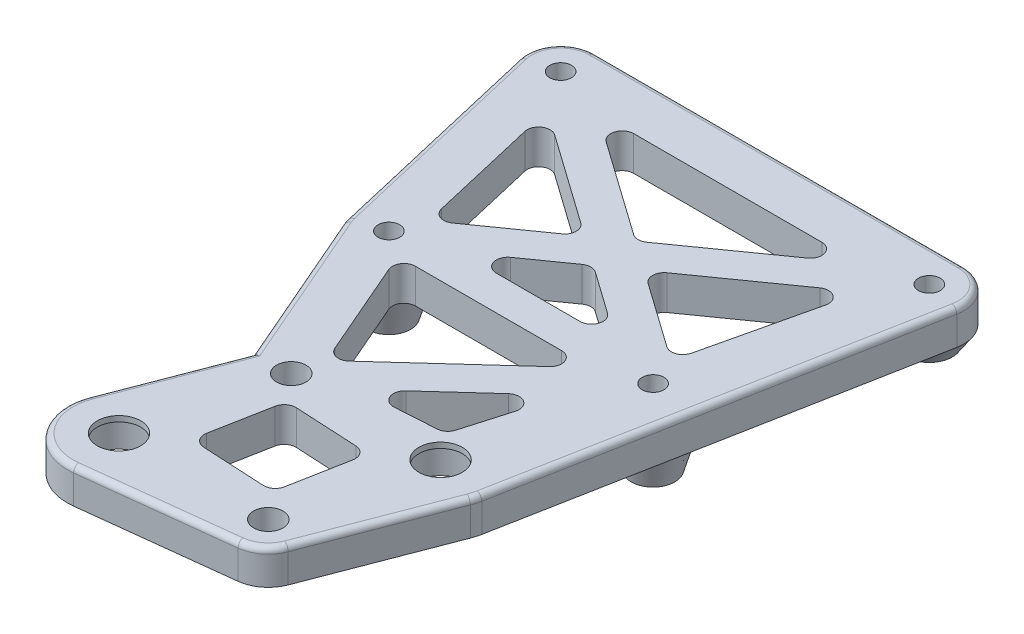
SolidWorks part; units mm, degrees
ref_plane "Front Plane" through (0, 0, 0) normal (0, 0, 1) x (1, 0, 0)
ref_plane "Top Plane" through (0, 0, 0) normal (0, 1, 0) x (1, 0, 0)
ref_plane "Right Plane" through (0, 0, 0) normal (1, 0, 0) x (0, 0, -1)
sketch "Sketch1" plane through (0, 0, 0) normal (0, 1, 0) x (1, 0, 0)
  line L0 (0, 0) -> (20.6375, 0) construction
  line L1 (20.6375, 0) -> (25.4, 19.05) construction
  line L2 (25.4, 19.05) -> (4.7625, 19.05) construction
  line L3 (4.7625, 19.05) -> (0, 0) construction
  line L8 (0.3164, 20.7568) -> (-6.6692, 2.5603)
  line L9 (4.213, 23.7807) -> (24.5757, 26.146)
  line L10 (32.0692, 16.4897) -> (25.0836, -1.7068)
  line L11 (0.8243, -7.096) -> (21.187, -4.7307)
  line L12 (0, 0) -> (25.4, 19.05) construction
  line L13 (4.7625, 19.05) -> (20.6375, 0) construction
  line L14 (7.5279, 4.1904) -> (16.2024, 3.7319)
  line L15 (17.8461, 5.0227) -> (19.3482, 12.9798)
  line L16 (17.8721, 14.8596) -> (9.1976, 15.3181)
  line L17 (7.5539, 14.0273) -> (6.0518, 6.0702)
  circle A0 centre (0, 0) radius 4.05
  circle A1 centre (25.4, 19.05) radius 4.05
  circle A2 centre (20.6375, 0) radius 2.032
  circle A3 centre (4.7625, 19.05) radius 2.032
  arc A4 (-6.6692, 2.5603) -> (0.8243, -7.096) centre (0, 0) ccw
  arc A5 (4.213, 23.7807) -> (0.3164, 20.7568) centre (4.7625, 19.05) ccw
  arc A6 (32.0692, 16.4897) -> (24.5757, 26.146) centre (25.4, 19.05) ccw
  arc A7 (21.187, -4.7307) -> (25.0836, -1.7068) centre (20.6375, 0) ccw
  arc A8 (7.5279, 4.1904) -> (6.0518, 6.0702) centre (7.6117, 5.7757) cw
  arc A9 (16.2024, 3.7319) -> (17.8461, 5.0227) centre (16.2862, 5.3172) ccw
  arc A10 (19.3482, 12.9798) -> (17.8721, 14.8596) centre (17.7883, 13.2743) ccw
  arc A11 (9.1976, 15.3181) -> (7.5539, 14.0273) centre (9.1138, 13.7328) ccw
  point P25 (5.715, 4.2863)
  point P28 (17.5886, 3.6587)
  point P31 (19.685, 14.7637)
  point P34 (7.8114, 15.3913)
  dimension "D4" = 8.1
  dimension "D5" = 4.064
  dimension "D6" = 7.1437
  dimension "D7" = 4.7625
  dimension "D12" = 1.5875
  dimension "D1" = 20.6375
  dimension "D2" = 19.05
  dimension "D3" = 4.7625
  dimension "D8" = 7.1437
  dimension "D9" = 7.1437
  dimension "D10" = 4.7625
  dimension "D11" = 4.7625
extrude "Boss-Extrude1" add sketch "Sketch1" along normal blind 4.7625
sketch "Sketch2" plane through (0, 4.7625, 0) normal (0, 1, 0) x (1, 0, 0)
  circle A0 centre (25.4, 19.05) radius 4.05 construction
  circle A1 centre (0, 0) radius 4.05 construction
  circle A2 centre (25.4, 19.05) radius 4.05
  circle A3 centre (0, 0) radius 4.05
  circle A4 centre (25.4, 19.05) radius 3
  circle A5 centre (0, 0) radius 3
  dimension "D1" = 6
extrude "Boss-Extrude2" add sketch "Sketch2" against normal blind 0.7625
sketch "Sketch3" plane through (0, 4.7625, 0) normal (0, 1, 0) x (1, 0, 0)
  line L0 (0, 0) -> (25.4, 19.05) construction
  line L1 (12.7, 9.525) -> (12.7, 24.7665) construction
  line L2 (24.5757, 26.146) -> (4.213, 23.7807) construction
  line L4 (-12.7775, 78.5812) -> (38.1775, 78.5812)
  line L5 (42.8571, 72.9341) -> (32.4194, 17.723)
  line L6 (0.3164, 20.7568) -> (-6.6692, 2.5603) construction
  line L7 (0.3164, 20.7568) -> (-0.3807, 18.941)
  line L8 (24.5757, 26.146) -> (4.213, 23.7807)
  line L9 (-0.3807, 18.941) -> (-9.9261, 40.9689)
  line L10 (-10.1942, 41.7806) -> (-17.4155, 72.7368)
  circle A0 centre (30.9562, 42.8625) radius 1.5
  circle A1 centre (25.4, 19.05) radius 3 construction
  circle A2 centre (-5.5563, 42.8625) radius 1.5
  circle A3 centre (-12.7775, 73.8187) radius 1.5
  circle A5 centre (38.1775, 73.8187) radius 1.5
  arc A6 (-12.7775, 78.5812) -> (-17.4155, 72.7368) centre (-12.7775, 73.8187) ccw
  arc A7 (42.8571, 72.9341) -> (38.1775, 78.5812) centre (38.1775, 73.8187) ccw
  arc A8 (21.187, -4.7307) -> (25.0836, -1.7068) centre (20.6375, 0) ccw construction
  arc A10 (32.0692, 16.4897) -> (24.5757, 26.146) centre (25.4, 19.05) ccw construction
  arc A14 (32.4194, 17.723) -> (24.5757, 26.146) centre (25.4, 19.05) ccw
  arc A15 (4.213, 23.7807) -> (0.3164, 20.7568) centre (4.7625, 19.05) ccw
  arc A16 (-10.1942, 41.7806) -> (-9.9261, 40.9689) centre (-5.5563, 42.8625) ccw
  point P6 (0, 0)
  point P24 (0, 0)
  dimension "D1" = 23.8125
  dimension "D2" = 5.5562
  dimension "D3" = 3
  dimension "D4" = 30.9562
  dimension "D5" = 7.2212
extrude "Boss-Extrude3" add sketch "Sketch3" against normal blind 4.7625
sketch "Sketch4" plane through (0, 4.7625, 0) normal (0, 1, 0) x (1, 0, 0)
  line L0 (-5.5563, 42.8625) -> (30.9562, 42.8625) construction
  line L1 (30.9562, 42.8625) -> (24.4148, 20.2948) construction
  line L2 (24.4148, 20.2948) -> (4.7625, 19.05) construction
  line L3 (4.7625, 19.05) -> (-5.5563, 42.8625) construction
  line L4 (4.7625, 19.05) -> (30.9562, 42.8625) construction
  line L5 (7.266, 24.544) -> (21.7585, 37.7191)
  line L6 (0.4889, 40.4812) -> (20.6907, 40.4812)
  line L7 (4.7415, 25.0875) -> (-0.9677, 38.2625)
  line L8 (5.6239, 23.0512) -> (24.7969, 40.4812) construction
  line L9 (5.6239, 23.0512) -> (-1.9292, 40.4812) construction
  line L10 (-1.9292, 40.4812) -> (24.7969, 40.4812) construction
  line L11 (14.7385, 24.9009) -> (22.1669, 31.654)
  line L12 (24.7595, 30.0374) -> (22.9044, 23.6373)
  line L13 (21.48, 22.4949) -> (15.9067, 22.1419)
  line L14 (11.3888, 21.8557) -> (26.3234, 35.4326) construction
  line L15 (22.5937, 22.5655) -> (11.3888, 21.8557) construction
  line L16 (26.3234, 35.4326) -> (22.5937, 22.5655) construction
  line L17 (-5.5563, 42.8625) -> (-12.7775, 73.8187) construction
  line L18 (-12.7775, 73.8187) -> (38.1775, 73.8187) construction
  line L19 (38.1775, 73.8187) -> (30.9562, 42.8625) construction
  line L20 (12.7, 55.7849) -> (38.1775, 73.8187) construction
  line L21 (12.7, 55.7849) -> (-12.7775, 73.8187) construction
  line L22 (-5.5563, 42.8625) -> (12.7, 55.7849) construction
  line L23 (12.7, 55.7849) -> (30.9562, 42.8625) construction
  line L31 (6.7478, 57.0807) -> (-5.6204, 65.8353)
  line L32 (-4.578, 49.151) -> (-8.0836, 64.1789)
  line L33 (-2.1148, 48.2159) -> (6.7478, 54.4892)
  line L34 (-0.3012, 71.4375) -> (25.7012, 71.4375)
  line L35 (13.6172, 59.3515) -> (26.6184, 68.5543)
  line L36 (11.7828, 59.3515) -> (-1.2184, 68.5543)
  line L37 (6.0028, 48.127) -> (11.7828, 52.2183)
  line L38 (13.6172, 52.2183) -> (19.3972, 48.127)
  line L39 (6.92, 45.2437) -> (18.48, 45.2437)
  line L40 (18.6522, 57.0807) -> (31.0204, 65.8353)
  line L41 (33.4836, 64.1789) -> (29.978, 49.151)
  line L42 (18.6522, 54.4892) -> (27.5148, 48.2159)
  line L43 (1.9295, 45.2437) -> (12.7, 52.8675) construction
  line L44 (1.9295, 45.2437) -> (23.4705, 45.2437) construction
  line L45 (12.7, 52.8675) -> (23.4705, 45.2437) construction
  line L46 (34.4335, 68.2512) -> (29.4417, 46.852) construction
  line L47 (16.8216, 55.7849) -> (29.4417, 46.852) construction
  line L48 (16.8216, 55.7849) -> (34.4335, 68.2512) construction
  line L49 (-5.2917, 71.4375) -> (30.6917, 71.4375) construction
  line L50 (12.7, 58.7023) -> (30.6917, 71.4375) construction
  line L51 (12.7, 58.7023) -> (-5.2917, 71.4375) construction
  line L52 (8.5784, 55.7849) -> (-9.0335, 68.2512) construction
  line L53 (-4.0417, 46.852) -> (8.5784, 55.7849) construction
  line L54 (-4.0417, 46.852) -> (-9.0335, 68.2512) construction
  line L55 (25.4, 19.05) -> (24.4148, 20.2948) construction
  line L56 (4.7625, 19.05) -> (25.4, 19.05) construction
  arc A0 (7.266, 24.544) -> (4.7415, 25.0875) centre (6.1981, 25.7187) cw
  arc A1 (21.7585, 37.7191) -> (20.6907, 40.4812) centre (20.6907, 38.8937) ccw
  arc A2 (0.4889, 40.4812) -> (-0.9677, 38.2625) centre (0.4889, 38.8937) ccw
  arc A3 (14.7385, 24.9009) -> (15.9067, 22.1419) centre (15.8063, 23.7262) ccw
  arc A4 (22.1669, 31.654) -> (24.7595, 30.0374) centre (23.2348, 30.4794) cw
  arc A5 (22.9044, 23.6373) -> (21.48, 22.4949) centre (21.3796, 24.0793) cw
  arc A12 (6.0028, 48.127) -> (6.92, 45.2437) centre (6.92, 46.8312) ccw
  arc A13 (11.7828, 52.2183) -> (13.6172, 52.2183) centre (12.7, 50.9225) cw
  arc A14 (19.3972, 48.127) -> (18.48, 45.2437) centre (18.48, 46.8312) cw
  arc A15 (29.978, 49.151) -> (27.5148, 48.2159) centre (28.432, 49.5116) cw
  arc A16 (18.6522, 57.0807) -> (18.6522, 54.4892) centre (19.5694, 55.7849) ccw
  arc A17 (31.0204, 65.8353) -> (33.4836, 64.1789) centre (31.9376, 64.5396) cw
  arc A18 (25.7012, 71.4375) -> (26.6184, 68.5543) centre (25.7012, 69.85) cw
  arc A19 (13.6172, 59.3515) -> (11.7828, 59.3515) centre (12.7, 60.6473) cw
  arc A20 (-0.3012, 71.4375) -> (-1.2184, 68.5543) centre (-0.3012, 69.85) ccw
  arc A21 (6.7478, 57.0807) -> (6.7478, 54.4892) centre (5.8306, 55.7849) cw
  arc A22 (-4.578, 49.151) -> (-2.1148, 48.2159) centre (-3.032, 49.5116) ccw
  arc A23 (-5.6204, 65.8353) -> (-8.0836, 64.1789) centre (-6.5376, 64.5396) ccw
  point P87 (24.2989, 20.2887)
  point P89 (23.6312, 21.4731)
  point P92 (32.5641, 30.649)
  dimension "D2" = 1.5875
  dimension "D4" = 1.5875
  dimension "D5" = 1.5875
  dimension "D10" = 1.5875
  dimension "D11" = 51.64
  dimension "D1" = 2.3813
  dimension "D3" = 2.3813
  dimension "D6" = 2.3813
  dimension "D7" = 2.3813
  dimension "D8" = 2.3813
  dimension "D9" = 2.3813
extrude "Cut-Extrude1" cut sketch "Sketch4" against normal through all
sketch "Sketch5" plane through (0, 0, 0) normal (0, -1, 0) x (1, 0, 0)
  circle A0 centre (-5.5563, -42.8625) radius 3
  circle A1 centre (-5.5563, -42.8625) radius 1.5 construction
  circle A2 centre (-5.5563, -42.8625) radius 1.5
  circle A3 centre (30.9562, -42.8625) radius 1.5 construction
  circle A4 centre (30.9562, -42.8625) radius 1.5
  circle A5 centre (30.9562, -42.8625) radius 3
  dimension "D1" = 6
extrude "Boss-Extrude4" add sketch "Sketch5" along normal blind 5.5245
chamfer "Chamfer1" distance 1.5875 distance2 5.5245 2 edges at (30.9562, 0, -39.8625) (-5.5563, 0, -39.8625) first distance on face at (30.9562, 0, -39.8625)
sketch "Sketch6" plane through (0, 0, 0) normal (0, -1, 0) x (1, 0, 0)
  circle A0 centre (38.1775, -73.8187) radius 1.5 construction
  circle A1 centre (-12.7775, -73.8187) radius 1.5 construction
  circle A2 centre (38.1775, -73.8187) radius 1.5
  circle A3 centre (-12.7775, -73.8187) radius 1.5
  circle A4 centre (-12.7775, -73.8187) radius 3.175
  circle A5 centre (38.1775, -73.8187) radius 3.175
  dimension "D1" = 6.35
extrude "Boss-Extrude5" add sketch "Sketch6" along normal blind 2.3495
chamfer "Chamfer2" distance 1.5875 distance2 2.3495 2 edges at (38.1775, 0, -70.6437) (-12.7775, 0, -70.6437) first distance on face at (38.1775, 0, -70.6437)
fillet "Fillet1" radius 0.7937 13 edges at (-3.525, 4.7625, -10.7507) (-5.6437, 4.7625, 4.3797) (11.0056, 4.7625, 5.9134) (23.5573, 4.7625, 3.7625) (28.5764, 4.7625, -7.3914) (32.272, 4.7625, -17.0985) (-5.1534, 4.7625, -29.955) (-10.0784, 4.7625, -41.3687) (-13.8048, 4.7625, -57.2587) (-16.508, 4.7625, -76.7792) (12.7, 4.7625, -78.5812) (41.8445, 4.7625, -76.8575) (37.6382, 4.7625, -45.3285)
equation "\"D9@Sketch1\"=\"D8@Sketch1\""
equation "\"D11@Sketch1\"=\"D10@Sketch1\""
